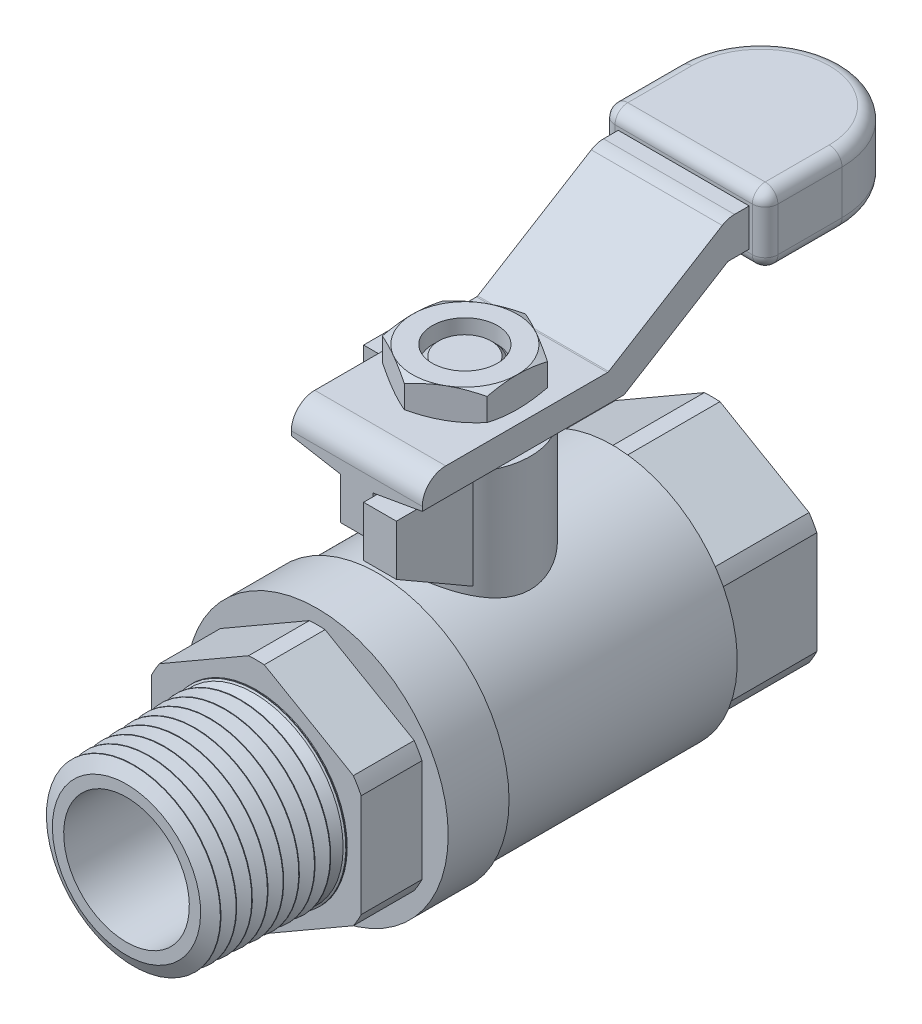
SolidWorks part; units mm, degrees
ref_plane "Front" through (0, 0, 0) normal (0, 0, 1) x (1, 0, 0)
ref_plane "Top" through (0, 0, 0) normal (0, 1, 0) x (1, 0, 0)
ref_plane "Right" through (0, 0, 0) normal (1, 0, 0) x (0, 0, -1)
sketch "Sketch1" plane through (0, -2.9295, 125.5668) normal (1, 0, 0) x (0, 0, -1)
  line L0 (139.5622, 2.9295) -> (139.5622, 11.7701)
  line L1 (139.5622, 11.7701) -> (140.4199, 13.3689) construction
  line L2 (140.4199, 13.3689) -> (141.3756, 11.8268) construction
  line L3 (141.3756, 11.8268) -> (142.2333, 13.4256) construction
  line L4 (142.2333, 13.4256) -> (143.189, 11.8835) construction
  line L5 (141.4083, 11.8877) -> (142.2006, 13.3646)
  line L6 (142.2006, 13.3646) -> (142.2697, 13.3668)
  line L7 (142.2697, 13.3668) -> (143.1526, 11.9422)
  line L8 (143.1526, 11.9422) -> (143.2217, 11.9444)
  line L9 (139.5622, 11.7701) -> (143.189, 11.8835) construction
  line L10 (140.4199, 13.3689) -> (142.2333, 13.4256) construction
  line L11 (139.9911, 12.5695) -> (142.7112, 12.6545) construction
  line L12 (139.5622, 2.9295) -> (125.5668, 2.9295) construction
  line L13 (143.2217, 11.9444) -> (144.014, 13.4213)
  line L14 (139.5949, 11.8311) -> (140.3872, 13.3079)
  line L15 (140.3872, 13.3079) -> (140.4563, 13.3101)
  line L16 (140.4563, 13.3101) -> (141.3392, 11.8856)
  line L17 (141.3392, 11.8856) -> (141.4083, 11.8877)
  line L18 (139.9911, 12.5695) -> (139.5622, 12.5561) construction
  line L19 (139.5622, 12.5561) -> (139.5622, 11.7701) construction
  line L20 (139.9911, -6.7105) -> (139.5622, -6.6971) construction
  line L21 (139.5949, 11.8311) -> (139.5622, 11.7701)
  line L22 (144.014, 13.4213) -> (144.0831, 13.4234)
  line L23 (144.0831, 13.4234) -> (144.966, 11.9989)
  line L24 (144.966, 11.9989) -> (145.0351, 12.0011)
  line L25 (145.0351, 12.0011) -> (145.8274, 13.478)
  line L26 (145.8274, 13.478) -> (145.8965, 13.4801)
  line L27 (145.8965, 13.4801) -> (146.7794, 12.0556)
  line L28 (146.7794, 12.0556) -> (146.8485, 12.0577)
  line L29 (146.8485, 12.0577) -> (147.6408, 13.5346)
  line L30 (147.6408, 13.5346) -> (147.7099, 13.5368)
  line L31 (147.7099, 13.5368) -> (148.5928, 12.1123)
  line L32 (148.5928, 12.1123) -> (148.6619, 12.1144)
  line L33 (148.6619, 12.1144) -> (149.4542, 13.5913)
  line L34 (149.4542, 13.5913) -> (149.5233, 13.5935)
  line L35 (149.5233, 13.5935) -> (150.4062, 12.1689)
  line L36 (150.4062, 12.1689) -> (150.4753, 12.1711)
  line L37 (150.4753, 12.1711) -> (151.2676, 13.648)
  line L38 (151.2676, 13.648) -> (151.3367, 13.6501)
  line L39 (151.3367, 13.6501) -> (152.2196, 12.2256)
  line L40 (152.2196, 12.2256) -> (152.2887, 12.2278)
  line L41 (152.2887, 12.2278) -> (153.081, 13.7046)
  line L42 (153.081, 13.7046) -> (153.1501, 13.7068)
  line L43 (153.1501, 13.7068) -> (154.033, 12.2823)
  line L44 (154.033, 12.2823) -> (154.1021, 12.2844)
  line L45 (154.1021, 12.2844) -> (154.8944, 13.7613)
  line L46 (154.8944, 13.7613) -> (154.9635, 13.7635)
  line L47 (154.9635, 13.7635) -> (155.8464, 12.3389)
  line L48 (155.8464, 12.3389) -> (155.9155, 12.3411)
  line L49 (155.9155, 12.3411) -> (156.7078, 13.818)
  line L50 (156.7078, 13.818) -> (156.7769, 13.8201)
  line L51 (156.7769, 13.8201) -> (157.6598, 12.3956)
  line L52 (157.6598, 12.3956) -> (157.7289, 12.3978)
  line L53 (157.7289, 12.3978) -> (158.5212, 13.8747)
  line L54 (158.5212, 13.8747) -> (158.5903, 13.8768)
  line L55 (158.5903, 13.8768) -> (159.4732, 12.4523)
  line L56 (159.4732, 12.4523) -> (159.5423, 12.4544)
  line L57 (159.5423, 12.4544) -> (160.3346, 13.9313)
  line L58 (160.3346, 13.9313) -> (160.4037, 13.9335)
  line L59 (160.4037, 13.9335) -> (161.2866, 12.509)
  line L60 (161.2866, 12.509) -> (161.3557, 12.5111)
  line L61 (161.3557, 12.5111) -> (162.148, 13.988)
  line L62 (162.148, 13.988) -> (162.2171, 13.9902)
  line L63 (162.2171, 13.9902) -> (163.1, 12.5656)
  line L64 (163.1, 12.5656) -> (163.1691, 12.5678)
  line L65 (163.1691, 12.5678) -> (163.9614, 14.0447)
  line L66 (163.9614, 14.0447) -> (164.0305, 14.0468)
  line L67 (164.0305, 14.0468) -> (164.9134, 12.6223)
  line L68 (164.9134, 12.6223) -> (164.9825, 12.6245)
  line L69 (164.9825, 12.6245) -> (165.7748, 14.1013)
  line L70 (165.7748, 14.1013) -> (165.8439, 14.1035)
  line L71 (165.8439, 14.1035) -> (166.7268, 12.679)
  line L72 (166.7268, 12.679) -> (166.7959, 12.6811)
  line L73 (139.5622, 2.9295) -> (166.7959, 2.9295)
  line L74 (166.7959, 2.9295) -> (166.7959, 12.6811)
  line L75 (140.4217, 13.309) -> (140.4199, 13.3689) construction
  line L76 (142.7112, 12.6545) -> (153.1258, 12.98) construction
  line L77 (153.1258, 12.98) -> (153.1258, 2.9295) construction
  line L78 (153.1258, 12.98) -> (155.0562, 13.0403) construction
  line L79 (155.0562, 13.0403) -> (155.0562, 2.9295) construction
  line L80 (125.5668, 2.9295) -> (85.2062, 2.9295) construction
  line L82 (85.2062, 2.9295) -> (85.2062, 13.0403) construction
  line L84 (153.1258, 12.2539) -> (155.0562, 12.3143) construction
  line L85 (139.5622, 7.3498) -> (125.5668, 7.3498) construction
  line L86 (125.5668, 7.3498) -> (125.5668, 2.9295) construction
  line L87 (155.0562, 13.0403) -> (85.2062, 13.0403) construction
  dimension "D1" = 60
  dimension "D2" = 0.0599
  dimension "E0" = 19.2532
  dimension "D3" = 0.0692
  dimension "Thread Pitch" = 1.8143
  dimension "D4" = 3.58
  dimension "D5" = 54.356
  dimension "L2 Thread Engagement" = 13.5636
  dimension "l Thread Length" = 15.494
  dimension "Body Length" = 69.85
  dimension "Right Length G" = 29.4894
revolve "Revolve1" add sketch "Sketch1" angle 360 about L12
sketch "Sketch6" plane through (0, 0, 0) normal (1, 0, 0) x (0, 0, -1)
  line L0 (29.4894, 0) -> (29.4894, 10.8369)
  line L1 (29.4894, 10.8369) -> (41.2291, 11.2038)
  line L2 (41.2291, 11.2038) -> (41.2291, 0)
  line L3 (41.2291, 0) -> (29.4894, 0)
  line L4 (29.4894, 10.1108) -> (29.4894, 0) construction
  line L5 (13.9954, 0) -> (41.2291, 0) construction
  line L6 (41.2291, 0) -> (41.2291, 9.7516) construction
  line L7 (31.1409, 10.8885) -> (31.2101, 10.8906) construction
revolve "Cut-Revolve3" cut sketch "Sketch6" angle 360 about L3
sketch "Sketch7" plane through (0, 0, 0) normal (1, 0, 0) x (0, 0, -1)
  line L0 (27.559, 9.3244) -> (29.4894, 10.8369)
  line L1 (29.4894, 10.8369) -> (29.4894, 9.3847)
  line L2 (29.4894, 9.3847) -> (27.559, 9.3244)
  line L3 (29.4894, 10.1108) -> (29.4894, 0) construction
  line L4 (14.8203, 10.3784) -> (14.8895, 10.3806) construction
  line L5 (27.559, 9.3244) -> (29.4894, 9.3847) construction
  line L6 (13.9954, 0) -> (27.559, 0) construction
  line L7 (27.559, 0) -> (27.559, 9.3244) construction
  line L8 (13.9954, 0) -> (13.9954, 8.8406) construction
  line L9 (0, 0) -> (13.9954, 0) construction
  line L10 (0, 0) -> (0, 7.493) construction
  line L11 (0, 7.493) -> (12.6478, 7.493) construction
  line L12 (13.9954, 0) -> (13.9954, 8.8406) construction
  line L13 (13.9954, 8.8406) -> (12.6478, 7.493) construction
  dimension "D1" = 45
  dimension "Min ID" = 14.986
revolve "Revolve3" add sketch "Sketch7" angle 360 about L6
pattern_linear "LPattern2" count 2 spacing 54.356 along (0, 0, 1) of bodies 114
sketch "Sketch30" plane through (0, 0, 0) normal (1, 0, 0) x (0, 0, -1)
  line L0 (-40.3606, 0) -> (-40.3606, 10.1108) construction
  line L1 (-40.3606, 7.493) -> (0, 7.493)
  line L2 (-40.3606, 7.493) -> (-40.3606, 0)
  line L3 (-40.3606, 0) -> (0, 0)
  line L4 (0, 7.493) -> (0, 0)
  line L5 (0, 7.493) -> (12.6478, 7.493) construction
  line L6 (13.9954, 0) -> (0, 0) construction
  line L7 (0, 4.4203) -> (0, 0) construction
revolve "Cut-Revolve8" cut sketch "Sketch30" angle 360 about L3
sketch "Sketch29" plane through (0, 0, 0) normal (1, 0, 0) x (0, 0, -1)
  line L0 (0, 0) -> (13.9954, 0) construction
  line L1 (13.9954, 0) -> (13.9954, 8.8406) construction
  line L2 (0, 7.493) -> (12.6478, 7.493) construction
  line L3 (13.9954, 8.8406) -> (12.6478, 7.493) construction
  line L4 (-24.8666, 0) -> (13.9954, 0)
  line L5 (13.9954, 0) -> (13.9954, 8.8406)
  line L6 (-24.8666, 7.493) -> (12.6478, 7.493)
  line L7 (13.9954, 8.8406) -> (12.6478, 7.493)
  line L8 (-24.8666, -10.8369) -> (-24.8666, 10.8369) construction
  line L9 (-24.8666, 0) -> (-24.8666, 7.493)
revolve "Revolve6" add sketch "Sketch29" angle 360 about L4
sketch "Sketch8" plane through (0, 0, 24.8666) normal (0, 0, 1) x (1, 0, 0)
  line L1 (0, 14.4301) -> (-12.4968, 7.215)
  line L2 (-12.4968, 7.215) -> (-12.4968, -7.215)
  line L3 (-12.4968, -7.215) -> (0, -14.4301)
  line L4 (0, -14.4301) -> (12.4968, -7.215)
  line L5 (12.4968, -7.215) -> (12.4968, 7.215)
  line L6 (12.4968, 7.215) -> (0, 14.4301)
  circle A0 centre (0, 0) radius 12.4968 construction
  dimension "Body Hex" = 24.9936
extrude "Extrude1" add sketch "Sketch8" against normal up to surface (54.356 mm away) separate body
sketch "Sketch9" plane through (0, 0, 0) normal (1, 0, 0) x (0, 0, -1)
  line L0 (-17.6095, 7.215) -> (-17.6095, 15.621)
  line L1 (-17.6095, 15.621) -> (-10.3523, 15.621)
  line L2 (-10.3523, 15.621) -> (-10.3523, 15.1811)
  line L3 (-10.3523, 15.1811) -> (-10.0412, 14.87)
  line L4 (-10.0412, 14.87) -> (17.624, 14.87)
  line L5 (17.624, 14.87) -> (17.624, 7.215)
  line L6 (17.624, 7.215) -> (-17.6095, 7.215)
  line L7 (29.4894, 7.215) -> (-24.8666, 7.215) construction
  line L8 (0, 0) -> (0, 7.215) construction
  line L9 (13.9954, 0) -> (13.9954, 8.8406) construction
  line L10 (0, 0) -> (-17.6095, 0) construction
  line L11 (-17.6095, 0) -> (-17.6095, 7.215) construction
  line L12 (-10.0412, 14.87) -> (-10.0412, 14.4301) construction
  line L13 (29.4894, 14.4301) -> (-24.8666, 14.4301) construction
  line L14 (29.4894, 10.1108) -> (29.4894, 14.87) construction
  line L15 (29.4894, 14.87) -> (17.624, 14.87) construction
  line L16 (-24.8666, 14.4301) -> (-24.8666, 15.621) construction
  line L17 (-24.8666, 15.621) -> (-17.6095, 15.621) construction
  dimension "D1" = 3.6286
  dimension "D2" = 31.242
  dimension "D3" = 135
  dimension "D4" = 7.2571
revolve "Revolve4" add sketch "Sketch9" angle 360 about L10
sketch "Sketch10" plane through (0, 0, 0) normal (1, 0, 0) x (0, 0, -1)
  line L0 (0, 7.493) -> (0, 23.8567)
  line L1 (3.8925, 26.4221) -> (3.9179, 26.4221) construction
  line L2 (7.8105, 26.4221) -> (7.8105, 7.493)
  line L3 (7.8105, 7.493) -> (0, 7.493)
  line L4 (0, 0) -> (0, 7.493) construction
  line L5 (-9.0805, 21.1485) -> (-9.0805, 26.6761) construction
  line L6 (-9.0805, 26.6761) -> (10.3505, 26.6761) construction
  line L7 (10.3505, 26.6761) -> (23.5567, 34.7738) construction
  line L8 (-9.0805, 21.1485) -> (-12.8905, 21.1485) construction
  line L9 (-12.8905, 21.1485) -> (-12.8905, 30.4861) construction
  line L10 (-12.8905, 30.4861) -> (9.2754, 30.4861) construction
  line L11 (9.2754, 30.4861) -> (23.5567, 39.243) construction
  line L12 (23.5567, 39.243) -> (23.5567, 34.7738) construction
  line L13 (17.624, 14.87) -> (-10.0412, 14.87) construction
  line L14 (23.5567, 41.148) -> (23.5567, 32.8688) construction
  line L15 (23.5567, 32.8688) -> (44.9834, 32.8688) construction
  line L16 (44.9834, 32.8688) -> (44.9834, 41.148) construction
  line L17 (44.9834, 41.148) -> (23.5567, 41.148) construction
  line L18 (-1.8075, 30.4861) -> (-1.8075, 26.6761) construction
  line L19 (16.416, 34.8645) -> (18.4076, 31.6165) construction
  line L20 (-7.8105, 26.4221) -> (-7.8105, 7.493) construction
  line L21 (0, 7.493) -> (12.6478, 7.493) construction
  line L22 (23.5567, 32.8688) -> (23.5567, 14.87) construction
  line L23 (29.4894, 14.87) -> (17.624, 14.87) construction
  line L24 (-10.3523, 15.621) -> (-10.3523, 21.1485) construction
  line L25 (-10.3523, 21.1485) -> (-12.8905, 21.1485) construction
  line L26 (3.8925, 26.4221) -> (3.8925, 32.8688)
  line L27 (3.8925, 32.8688) -> (0, 32.8688)
  line L28 (3.8925, 26.4221) -> (3.8925, 23.8821)
  line L29 (3.8925, 23.8821) -> (0, 23.8821)
  line L30 (0, 23.8567) -> (3.9179, 23.8567)
  line L31 (3.9179, 23.8567) -> (3.9179, 26.4221)
  line L32 (3.9179, 26.4221) -> (7.8105, 26.4221)
  line L33 (0, 23.8567) -> (0, 23.8821) construction
  line L34 (0, 23.8821) -> (0, 32.8688)
  line L35 (-3.8925, 26.4221) -> (-3.8925, 32.8688) construction
  line L36 (3.9179, 23.8567) -> (3.9179, 14.87) construction
  line L37 (3.9179, 14.87) -> (23.5567, 14.87) construction
  point P26 (23.5567, 37.0084)
  dimension "Handle Height" = 41.148
  dimension "D2" = 1.905
  dimension "Handle Length" = 44.9834
  dimension "D3" = 15.621
  dimension "D5" = 17.9988
  dimension "D6" = 3.81
  dimension "D7" = 1.27
  dimension "D8" = 0.254
  dimension "D9" = 2.54
  dimension "D11" = 0.0254
  dimension "D12" = 0.0254
  dimension "D13" = 8.9867
  dimension "D14" = 2.54
revolve "Revolve5" add sketch "Sketch10" angle 360 about L4
chamfer "Chamfer1" distance 0.762 angle 45 1 edges at (0, 32.8688, -3.8925)
sketch "Sketch20" plane through (0, 0, 0) normal (1, 0, 0) x (0, 0, -1)
  line L0 (3.8925, 32.8688) -> (-3.8926, 32.8688) construction
  line L1 (-3.8926, 32.8688) -> (-3.8925, 32.075) construction
  line L2 (-3.8925, 32.075) -> (3.8925, 32.8688) construction
  line L3 (3.8925, 32.8688) -> (3.9026, 32.7701) construction
  line L4 (3.9026, 32.7701) -> (3.9731, 32.0791)
  line L5 (3.9731, 32.0791) -> (3.5205, 32.2823)
  line L6 (3.5205, 32.2823) -> (3.5004, 32.4797)
  line L7 (3.5004, 32.4797) -> (3.9026, 32.7701)
  line L8 (3.5104, 32.381) -> (3.9378, 32.4246) construction
  line L9 (3.8925, 32.8688) -> (3.8926, 32.42) construction
  line L10 (3.8926, 32.42) -> (-3.8925, 31.6262) construction
  line L11 (-3.8925, 31.6262) -> (-3.8925, 32.075) construction
  line L12 (-0.0862, 32.8688) -> (0.0862, 31.1774) construction
  line L13 (-3.8925, 26.4221) -> (-3.8925, 32.8688) construction
  line L14 (3.8925, 26.4221) -> (3.8925, 32.8688) construction
  line L15 (3.8925, 32.8688) -> (0, 32.8688) construction
  point P13 (0, 32.0231)
  dimension "D1" = 0.0992
  dimension "D2" = 0.1984
  dimension "D3" = 0.7937
  dimension "D4" = 60
  dimension "D5" = 0.7937
revolve "Cut-Revolve6" cut sketch "Sketch20" angle 360 about L12
pattern_linear "LPattern1" count 2 spacing 0.7937 along (0, 1, 0) count 11 spacing 0.7937 along (0, -1, 0) of "Cut-Revolve6"
sketch "Sketch26" plane through (0, 23.8567, 0) normal (0, 1, 0) x (-1, 0, 0)
  circle A1 centre (0, 0) radius 3.9179
  circle A2 centre (0, 0) radius 3.9179
  dimension "D1" = 0
extrude "Extrude8" add sketch "Sketch26" along normal blind 0.127
sketch "Sketch16" plane through (0, 0, 0) normal (1, 0, 0) x (0, 0, -1)
  line L0 (-24.8666, 7.215) -> (-24.8666, 14.4301) construction
  line L1 (29.4894, 14.4301) -> (17.624, 14.4301)
  line L2 (29.4894, 14.4301) -> (29.4894, 13.9221)
  line L3 (29.4894, 13.9221) -> (17.624, 13.9221)
  line L4 (17.624, 14.4301) -> (17.624, 13.9221)
  line L5 (-24.8666, 14.4301) -> (-17.6095, 14.4301)
  line L6 (-24.8666, 14.4301) -> (-24.8666, 13.9221)
  line L7 (-24.8666, 13.9221) -> (-17.6095, 13.9221)
  line L8 (-17.6095, 14.4301) -> (-17.6095, 13.9221)
  line L9 (29.4894, 14.4301) -> (29.4894, 7.215) construction
  line L10 (17.624, -14.87) -> (17.624, 14.87) construction
  line L11 (-17.6095, 15.621) -> (-17.6095, -15.621) construction
  line L12 (-17.6095, 14.4301) -> (-24.8666, 14.4301) construction
  line L13 (0, 0) -> (-24.8666, 0) construction
  line L14 (-24.8666, 0) -> (-24.8666, 13.9221) construction
  dimension "D1" = 0.508
revolve "Cut-Revolve5" cut sketch "Sketch16" angle 360 about L13
combine bodies "Combine1" operation type subtract main body 126 bodies to subtract 151
combine bodies "Combine2" operation type add bodies to combine 150 123
sketch "Sketch11" plane through (0, 0, 0) normal (1, 0, 0) x (0, 0, -1)
  line L1 (9.2754, 30.4861) -> (23.5567, 39.243) construction
  line L2 (10.3505, 26.6761) -> (23.5567, 34.7738) construction
  line L3 (-9.0805, 26.6761) -> (10.3505, 26.6761) construction
  line L4 (-9.0805, 21.1485) -> (-9.0805, 26.6761) construction
  line L5 (-12.8905, 30.4861) -> (9.2754, 30.4861) construction
  line L6 (-12.8905, 21.1485) -> (-12.8905, 30.4861) construction
  line L7 (43.0784, 34.7738) -> (43.0784, 39.243)
  line L8 (9.2754, 30.4861) -> (23.5567, 39.243)
  line L9 (10.3505, 26.6761) -> (23.5567, 34.7738)
  line L10 (-9.0805, 26.6761) -> (10.3505, 26.6761)
  line L11 (-9.0805, 21.1485) -> (-9.0805, 26.6761)
  line L12 (-12.8905, 30.4861) -> (9.2754, 30.4861)
  line L13 (-12.8905, 21.1485) -> (-12.8905, 30.4861)
  line L14 (-9.0805, 21.1485) -> (-12.8905, 21.1485) construction
  line L15 (-9.0805, 21.1485) -> (-12.8905, 21.1485)
  line L16 (23.5567, 39.243) -> (43.0784, 39.243)
  line L17 (23.5567, 34.7738) -> (43.0784, 34.7738)
  line L18 (44.9834, 32.8688) -> (44.9834, 41.148) construction
  dimension "D1" = 1.905
extrude "Extrude2" add sketch "Sketch11" along normal mid plane 15.621 separate body
sketch "Sketch21" plane through (0, 30.4861, 0) normal (0, 1, 0) x (-1, 0, 0)
  circle A0 centre (0, 0) radius 3.918
extrude "Cut-Extrude1" cut sketch "Sketch21" against normal through all
fillet "Fillet1" radius 0.254 3 edges at (0, 34.7738, -23.5567) (0, 30.4861, -9.2754) (0, 26.6761, 9.0805)
fillet "Fillet2" radius 2.794 3 edges at (0, 30.4861, 12.8905) (0, 39.243, -23.5567) (0, 26.6761, -10.3505)
fillet "Fillet3" radius 7.8105 2 edges at (-7.8105, 37.0084, -43.0784) (7.8105, 37.0084, -43.0784)
sketch "Sketch12" plane through (0, 39.243, 0) normal (0, 1, 0) x (-1, 0, 0)
  line L0 (9.7155, -26.0967) -> (-9.7155, -26.0967)
  line L1 (-9.7155, -26.0967) -> (-9.7155, -35.2679)
  line L2 (9.7155, -35.2679) -> (9.7155, -26.0967)
  line L3 (-7.8105, -35.2679) -> (-7.8105, -24.3451) construction
  line L4 (0, -44.9834) -> (0, -23.5567) construction
  arc A0 (-9.7155, -35.2679) -> (9.7155, -35.2679) centre (0, -35.2679) ccw
  arc A1 (-7.8105, -35.2679) -> (0, -43.0784) centre (0, -35.2679) ccw construction
  dimension "D1" = 1.905
  dimension "D2" = 2.54
extrude "Extrude3" add sketch "Sketch12" along normal blind 1.905 separate body
sketch "Sketch13" plane through (0, 34.7738, 0) normal (0, -1, 0) x (1, 0, 0)
  line L3 (9.7155, -26.0967) -> (-9.7155, -26.0967)
  line L4 (9.7155, -35.2679) -> (9.7155, -26.0967)
  line L5 (-9.7155, -26.0967) -> (-9.7155, -35.2679)
  line L6 (9.7155, -26.0967) -> (-9.7155, -26.0967)
  line L7 (9.7155, -35.2679) -> (9.7155, -26.0967)
  line L8 (-9.7155, -26.0967) -> (-9.7155, -35.2679)
  arc A1 (-9.7155, -35.2679) -> (9.7155, -35.2679) centre (0, -35.2679) ccw
  arc A2 (-9.7155, -35.2679) -> (9.7155, -35.2679) centre (0, -35.2679) ccw
  dimension "D1" = 0
extrude "Extrude4" add sketch "Sketch13" along normal blind 1.905 separate body
sketch "Sketch14" plane through (0, 39.243, 0) normal (0, -1, 0) x (1, 0, 0)
  line L0 (-7.8105, -35.2679) -> (-7.8105, -24.3451) construction
  line L1 (7.8105, -35.2679) -> (7.8105, -24.3451) construction
  line L2 (-7.8105, -35.2679) -> (-7.8105, -26.0967)
  line L3 (9.7155, -26.0967) -> (-9.7155, -26.0967)
  line L4 (9.7155, -35.2679) -> (9.7155, -26.0967)
  line L5 (-9.7155, -26.0967) -> (-9.7155, -35.2679)
  line L6 (9.7155, -26.0967) -> (7.8105, -26.0967)
  line L7 (9.7155, -35.2679) -> (9.7155, -26.0967)
  line L8 (-9.7155, -26.0967) -> (-9.7155, -35.2679)
  line L9 (7.8105, -35.2679) -> (7.8105, -26.0967)
  line L10 (-7.8105, -26.0967) -> (-9.7155, -26.0967)
  arc A0 (-7.8105, -35.2679) -> (0, -43.0784) centre (0, -35.2679) ccw construction
  arc A1 (-9.7155, -35.2679) -> (9.7155, -35.2679) centre (0, -35.2679) ccw
  arc A2 (-9.7155, -35.2679) -> (9.7155, -35.2679) centre (0, -35.2679) ccw
  arc A3 (0, -43.0784) -> (7.8105, -35.2679) centre (0, -35.2679) ccw construction
  arc A4 (-7.8105, -35.2679) -> (0, -43.0784) centre (0, -35.2679) ccw
  arc A5 (0, -43.0784) -> (7.8105, -35.2679) centre (0, -35.2679) ccw
  dimension "D1" = 0
extrude "Extrude5" add sketch "Sketch14" along normal up to surface (4.4692 mm away) up to face at (0, 34.7738, -33.1112)
fillet "Fillet4" radius 1.524 10 edges at (-9.7155, 41.148, -30.6823) (0, 41.148, -44.9834) (-9.7155, 32.8688, -30.6823) (0, 32.8688, -44.9834) (9.7155, 41.148, -30.6823) (9.7155, 32.8688, -30.6823) (9.7155, 37.0084, -26.0967) (-9.7155, 37.0084, -26.0967) (0, 41.148, -26.0967) (0, 32.8688, -26.0967)
sketch "Sketch15" plane through (0, 30.4861, 0) normal (0, 1, 0) x (-1, 0, 0)
  line L1 (0, 7.215) -> (-6.2484, 3.6075)
  line L2 (-6.2484, 3.6075) -> (-6.2484, -3.6075)
  line L3 (-6.2484, -3.6075) -> (0, -7.215)
  line L4 (0, -7.215) -> (6.2484, -3.6075)
  line L5 (6.2484, -3.6075) -> (6.2484, 3.6075)
  line L6 (6.2484, 3.6075) -> (0, 7.215)
  circle A0 centre (0, 0) radius 6.2484 construction
  dimension "D1" = 12.4968
extrude "Extrude6" add sketch "Sketch15" along normal blind 3.5947 separate body
sketch "Sketch22" plane through (0, 0, 0) normal (1, 0, 0) x (0, 0, -1)
  line L0 (6.2484, 34.0808) -> (7.215, 34.0808)
  line L1 (0, 34.0808) -> (3.8925, 34.0808)
  line L2 (0, 34.0808) -> (0, 30.4861)
  line L3 (0, 30.4861) -> (3.8925, 30.4861)
  line L4 (3.8925, 34.0808) -> (3.8925, 30.4861)
  line L5 (7.215, 34.0808) -> (7.215, 33.63)
  line L6 (7.215, 33.63) -> (6.2484, 34.0808)
  line L7 (6.2484, 30.4861) -> (7.215, 30.4861)
  line L8 (7.215, 30.4861) -> (7.215, 30.9368)
  line L9 (7.215, 30.9368) -> (6.2484, 30.4861)
  line L10 (7.215, 34.0808) -> (7.215, 30.4861) construction
  line L11 (3.6075, 34.0808) -> (7.215, 34.0808) construction
  line L12 (-12.8905, 30.4861) -> (9.2754, 30.4861) construction
  line L13 (0, 23.8821) -> (0, 32.8688) construction
  line L14 (3.8925, 26.4221) -> (3.8925, 32.8688) construction
  line L15 (0, 0) -> (0, 30.4861) construction
  line L16 (6.2484, 30.4861) -> (6.2484, 34.0808) construction
  dimension "D1" = 25
  dimension "D2" = 12.4968
revolve "Cut-Revolve7" cut sketch "Sketch22" angle 360 about L15
sketch "Sketch23" plane through (0, 0, 12.8905) normal (0, 0, 1) x (1, 0, 0)
  line L0 (-7.8105, 27.1841) -> (-1.9526, 26.1512)
  line L1 (-1.9526, 26.1512) -> (-1.9526, 21.1485)
  line L2 (-1.9526, 21.1485) -> (1.9526, 21.1485)
  line L3 (1.9526, 21.1485) -> (1.9526, 26.1512)
  line L4 (1.9526, 26.1512) -> (7.8105, 27.1841)
  line L5 (7.8105, 27.1841) -> (7.8105, 19.8785)
  line L6 (7.8105, 19.8785) -> (-7.8105, 19.8785)
  line L7 (-7.8105, 19.8785) -> (-7.8105, 27.1841)
  line L8 (-1.9526, 21.1485) -> (-7.8105, 21.1485) construction
  line L9 (1.9526, 21.1485) -> (7.8105, 21.1485) construction
  line L10 (0, 21.1485) -> (0, 19.8785) construction
  line L11 (-7.8105, 27.1841) -> (7.8105, 27.1841) construction
  line L12 (-1.9526, 26.1512) -> (1.9526, 26.1512) construction
  line L13 (-7.8105, 27.6921) -> (-7.8105, 21.1485) construction
  line L14 (7.8105, 27.6921) -> (7.8105, 21.1485) construction
  line L15 (7.8105, 21.1485) -> (-7.8105, 21.1485) construction
  line L16 (7.8105, 27.6921) -> (-7.8105, 27.6921) construction
  dimension "D1" = 3.9052
  dimension "D2" = 10
  dimension "D3" = 0.508
  dimension "D4" = 1.27
  dimension "D5" = 15.621
extrude "Cut-Extrude2" cut sketch "Sketch23" against normal through all
sketch "Sketch24" plane through (0, 0, 12.8905) normal (0, 0, 1) x (1, 0, 0)
  line L0 (-1.9526, 26.1512) -> (1.9526, 26.1512) construction
  line L1 (2.0796, 25.8972) -> (5.9849, 25.8972)
  line L2 (2.0796, 25.8972) -> (2.0796, 19.8785)
  line L3 (2.0796, 19.8785) -> (5.9849, 19.8785)
  line L4 (5.9849, 25.8972) -> (5.9849, 19.8785)
  line L6 (-1.9526, 21.1485) -> (1.9526, 21.1485) construction
  line L8 (1.9526, 21.1485) -> (1.9526, 26.1512) construction
  dimension "D1" = 0.254
  dimension "D2" = 0.127
  dimension "D3" = 1.27
  dimension "D4" = 3.9052
extrude "Extrude7" add sketch "Sketch24" along normal blind 1.27 and the other way up to surface other way up to face at (0.692, 14.8539, 7.7798)
ref_axis "Axis1" through (0, -15.2056, 0) along (0, 1, 0)
ref_plane "Plane1" through (0, 0, 0) normal (-0.7071, 0, -0.7071) x (-0.7071, 0, 0.7071)
mirror "Mirror3" about plane through (0, 0, 0) normal (-0.7071, 0, -0.7071) of "Extrude7"
draft "Draft1" type of draft neutral plane draft angle 30 faces to draft 1 face at (4.0799, 19.8785, 10.2912) neutral plane through (2.0796, 19.8785, 14.1605) neutral plane normal (0, 0, 1) parameters "D1"=30
draft "Draft2" type of draft neutral plane draft angle 30 faces to draft 1 face at (-10.2912, 19.8785, -4.0799) neutral plane through (-14.1605, 19.8785, -2.0796) neutral plane normal (-1, 0, 0) parameters "D1"=30
equation "\"D2@Sketch1\"=\"Thread Pitch@Sketch1\"*.033"
equation "\"D2@Sketch9\"=\"Body Hex@Sketch8\"*1.25"
equation "\"D1@Sketch9\" = \"Thread Pitch@Sketch1\"*2"
equation "\"D4@Sketch9\"=\"D1@Sketch9\"*2"
equation "\"D3@Sketch10\"=\"Body Hex@Sketch8\"*.625"
equation "\"D1@Extrude2\"=\"D3@Sketch10\""
equation "\"D1@Fillet3\"=\"D1@Extrude2\"/2"
equation "\"D1@Sketch15\"=\"D1@Extrude2\"*.8"
equation "\"D2@LPattern1\"=\"D13@Sketch10\"/\"D3@Sketch20\""
equation "\"D2@Sketch22\"=\"D1@Sketch15\""
equation "\"D1@Extrude6\"=\"D13@Sketch10\"/2.5"
equation "\"D1@Sketch23\"=\"D5@Sketch23\"/4"
equation "\"D4@Sketch24\"=\"D1@Sketch23\""
equation "\"D3@LPattern2\"=\"D5@Sketch1\""
